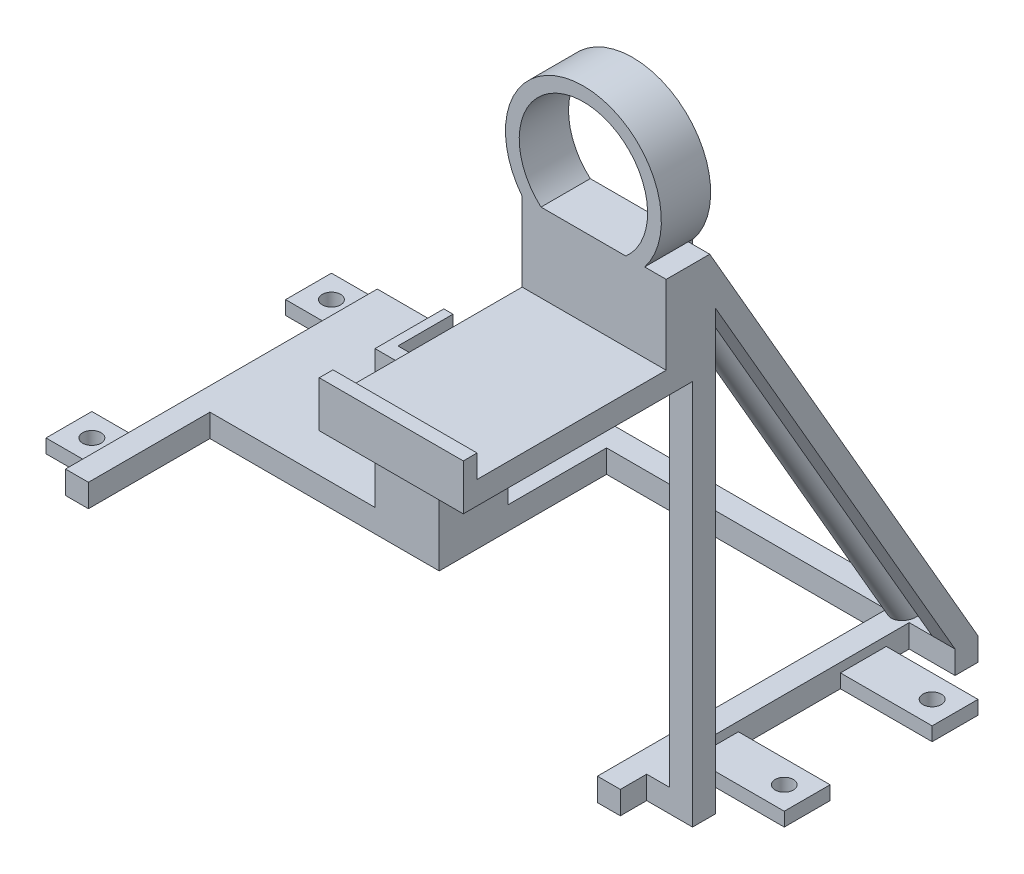
SolidWorks part; units mm, degrees
note: The reader was unsure of these and kept them because the rebuilt part matched: shared geometry of "Sketch23<2>".
ref_plane "Front Plane" through (0, 0, 0) normal (0, 0, 1) x (1, 0, 0)
ref_plane "Top Plane" through (0, 0, 0) normal (0, 1, 0) x (1, 0, 0)
ref_plane "Right Plane" through (0, 0, 0) normal (1, 0, 0) x (0, 0, -1)
sketch "Sketch1" plane through (0, 0, 0) normal (0, 1, 0) x (1, 0, 0)
  line L1 (0, 0) -> (121, 0)
  line L2 (0, 0) -> (0, -68)
  line L3 (0, -68) -> (121, -68)
  line L4 (121, 0) -> (121, -68)
  line L5 (5, -68) -> (116, -68)
  line L6 (5, -68) -> (5, -5)
  line L7 (5, -5) -> (116, -5)
  line L8 (116, -68) -> (116, -5)
  dimension "D1" = 121
  dimension "D2" = 68
  dimension "D3" = 5
  dimension "D4" = 5
  dimension "D5" = 5
extrude "Boss-Extrude1" add sketch "Sketch1" along normal blind 5 contours L8 L3 L4 L1 L2 L6 L7
ref_plane "Plane1" through (0, 3.75, 2.1651) normal (0, 0.866, 0.5) x (1, 0, 0)
sketch "Sketch2" plane through (0, 3.75, 2.1651) normal (0, 0.866, 0.5) x (1, 0, 0)
  line L2 (121, 2.5) -> (121, -56.3897) construction
  line L3 (0, 2.5) -> (121, 2.5) construction
  circle A0 centre (118.2001, -0.2999) radius 2.5
  dimension "D1" = 5
  dimension "D2" = 2.7999
  dimension "D3" = 2.7999
extrude "Boss-Extrude2" add sketch "Sketch2" along normal blind 100
ref_plane "Plane2" through (0, 0, 68) normal (0, 0, 1) x (1, 0, 0)
sketch "Sketch3" plane through (121, 0, 0) normal (1, 0, 0) x (0, 0, -1)
  line L0 (0, 5) -> (-68, 5) construction
  line L1 (0, 0) -> (-5, 0)
  line L2 (0, 0) -> (0, 5)
  line L3 (0, 5) -> (-5, 5)
  line L4 (-5, 0) -> (-5, 5)
  dimension "D1" = 5
extrude "Boss-Extrude3" add sketch "Sketch3" along normal blind 10
sketch "Sketch5" plane through (0, 3.75, 2.1651) normal (0, 0.866, 0.5) x (1, 0, 0)
  line L0 (131, -1.8301) -> (121, -1.8301) construction
  line L1 (131, 2.5) -> (126, 2.5)
  line L2 (131, 2.5) -> (131, -1.8301)
  line L3 (131, -1.8301) -> (126, -1.8301)
  line L4 (126, 2.5) -> (126, -1.8301)
  dimension "D1" = 5
extrude "Boss-Extrude4" add sketch "Sketch5" along normal offset from surface (117 mm away) 17 up to face at (118.2001, 88.9526, 54.5898) offset beyond the face yes
sketch "Sketch6" plane through (0, 1.25, -2.1651) normal (0, 0.5, -0.866) x (-1, 0, 0)
  line L0 (-126, 121.3301) -> (-126, 4.3301) construction
  line L1 (-131, 121.3301) -> (-126, 121.3301)
  line L2 (-131, 121.3301) -> (-131, 116.3301)
  line L3 (-131, 116.3301) -> (-126, 116.3301)
  line L4 (-126, 121.3301) -> (-126, 116.3301)
  dimension "D1" = 5
extrude "Boss-Extrude5" add sketch "Sketch6" along normal blind 20
sketch "Sketch7" plane through (126, 0, 0) normal (-1, 0, 0) x (0, 0, 1)
  line L0 (45.5096, 113.825) -> (41.1795, 116.325)
  line L1 (41.1795, 116.325) -> (62.25, 104.1599) construction
  line L2 (41.1795, 116.325) -> (38.6795, 111.9948)
  line L3 (38.6795, 111.9948) -> (43.0096, 109.4948)
  line L4 (38.6795, 111.9948) -> (56, 101.9948) construction
  line L5 (43.0096, 109.4948) -> (45.5096, 113.825)
  dimension "D1" = 90
  dimension "D2" = 5
extrude "Boss-Extrude6" add sketch "Sketch7" along normal blind 15
sketch "Sketch9" plane through (121, 0, 0) normal (1, 0, 0) x (0, 0, -1)
  line L0 (-62.25, 104.1599) -> (-62.25, 5) construction
  line L1 (-5, 5) -> (-68, 5) construction
  line L2 (-5, 0) -> (-68, 0) construction
  line L3 (-62.25, 5) -> (-57.25, 5)
  line L4 (-62.25, 5) -> (-62.25, 0)
  line L5 (-62.25, 0) -> (-57.25, 0)
  line L6 (-57.25, 5) -> (-57.25, 0)
  dimension "D1" = 5
extrude "Boss-Extrude7" add sketch "Sketch9" along normal up to surface (10 mm away) up to face at (131, 55.5593, 26.0136)
sketch "Sketch10" plane through (0, 5, 0) normal (0, 1, 0) x (1, 0, 0)
  line L0 (131, -57.25) -> (121, -57.25) construction
  line L1 (126, -57.25) -> (131, -57.25)
  line L2 (126, -57.25) -> (126, -62.25)
  line L3 (126, -62.25) -> (131, -62.25)
  line L4 (131, -57.25) -> (131, -62.25)
extrude "Boss-Extrude8" add sketch "Sketch10" along normal up to vertex
sketch "Sketch11" plane through (0, 0, 0) normal (-1, 0, 0) x (0, 0, 1)
  line L1 (62.25, 0) -> (52.25, 0)
  line L2 (62.25, 0) -> (62.25, 3)
  line L3 (62.25, 3) -> (52.25, 3)
  line L4 (52.25, 0) -> (52.25, 3)
  line L5 (0, 0) -> (10, 0)
  line L6 (0, 0) -> (0, 3)
  line L7 (0, 3) -> (10, 3)
  line L8 (10, 0) -> (10, 3)
  dimension "D1" = 10
  dimension "D2" = 3
  dimension "D3" = 10
  dimension "D4" = 3
extrude "Boss-Extrude9" add sketch "Sketch11" along normal blind 10
sketch "Sketch13" plane through (0, 3, 0) normal (0, 1, 0) x (1, 0, 0)
  line L0 (-5, -3) -> (-5, 0) construction
  line L1 (-10, 0) -> (0, 0) construction
  line L2 (-7, -5) -> (-10, -5) construction
  line L3 (-10, -10) -> (-10, 0) construction
  line L4 (-7, -57.25) -> (-10, -57.25) construction
  line L5 (-10, -62.25) -> (-10, -52.25) construction
  circle A0 centre (-5, -5) radius 2
  circle A1 centre (-5, -57.25) radius 2
  dimension "D1" = 4
extrude "Cut-Extrude1" cut sketch "Sketch13" against normal through all both and the other way through all
sketch "Sketch14" plane through (121, 0, 0) normal (1, 0, 0) x (0, 0, -1)
  line L0 (-5, 0) -> (-57.25, 0) construction
  line L1 (-20, 0) -> (-10, 0)
  line L2 (-20, 0) -> (-20, 3)
  line L3 (-20, 3) -> (-10, 3)
  line L4 (-10, 0) -> (-10, 3)
  line L5 (-57.25, 0) -> (-57.25, 5) construction
  line L6 (-42.25, 0) -> (-52.25, 0)
  line L7 (-42.25, 0) -> (-42.25, 3)
  line L8 (-42.25, 3) -> (-52.25, 3)
  line L9 (-52.25, 0) -> (-52.25, 3)
  line L10 (-5, 5) -> (-5, 0) construction
  dimension "D1" = 10
  dimension "D2" = 3
  dimension "D3" = 10
  dimension "D4" = 3
  dimension "D5" = 5
  dimension "D6" = 5
extrude "Boss-Extrude10" add sketch "Sketch14" along normal blind 20
sketch "Sketch15" plane through (0, 3, 0) normal (0, 1, 0) x (1, 0, 0)
  line L0 (138, -15) -> (141, -15) construction
  line L1 (141, -10) -> (141, -20) construction
  line L2 (136, -13) -> (136, -10) construction
  line L3 (141, -10) -> (121, -10) construction
  line L4 (136, -45.25) -> (136, -42.25) construction
  line L5 (141, -42.25) -> (121, -42.25) construction
  line L6 (138, -47.25) -> (141, -47.25) construction
  line L7 (141, -42.25) -> (141, -52.25) construction
  circle A0 centre (136, -15) radius 2
  circle A1 centre (136, -47.25) radius 2
  point P22 (141, -47.25)
  dimension "D1" = 4
extrude "Cut-Extrude2" cut sketch "Sketch15" against normal through all both and the other way through all
sketch "Sketch16" plane through (126, 0, 0) normal (-1, 0, 0) x (0, 0, 1)
  line L0 (49.8397, 111.325) -> (67, 101.4175)
  line L1 (49.8397, 111.325) -> (47.3397, 106.9948)
  line L2 (67, 101.4175) -> (64.5, 97.0874)
  line L3 (47.3397, 106.9948) -> (64.5, 97.0874)
  line L4 (45.5096, 113.825) -> (62.25, 104.1599) construction
  line L5 (43.0096, 109.4948) -> (56, 101.9948) construction
  line L6 (68, -54.223) -> (68, 54.223) construction
  line L7 (43.0096, 109.4948) -> (45.5096, 113.825) construction
  point P13 (44.2596, 111.6599)
  dimension "D1" = 1
  dimension "D2" = 90
  dimension "D3" = 5
extrude "Boss-Extrude11" add sketch "Sketch16" along normal blind 7.8
sketch "Sketch17" plane through (0, 105.075, 60.6651) normal (0, 0.866, 0.5) x (1, 0, 0)
  line L1 (131, 22.5) -> (108.821, 22.5)
  line L2 (131, 22.5) -> (131, 2.5)
  line L3 (131, 2.5) -> (108.821, 2.5)
  line L4 (108.821, 22.5) -> (108.821, 2.5)
  line L5 (0, 2.5) -> (126, 2.5) construction
extrude "Cut-Extrude3" cut sketch "Sketch17" against normal through all both and the other way through all
sketch "Sketch18" plane through (0, 0, 62.25) normal (0, 0, 1) x (1, 0, 0)
  line L0 (126, 104.1599) -> (118.2, 104.1599)
  line L1 (118.2, 104.1599) -> (102.2, 104.1599) construction
  line L2 (102.2, 104.1599) -> (100.7, 104.1599)
  arc A0 (102.2, 104.1599) -> (118.2, 104.1599) centre (110.2, 104.1599) cw
  arc A1 (100.7, 104.1599) -> (119.7, 104.1599) centre (110.2, 104.1599) cw
  dimension "D1" = 7.8
  dimension "D2" = 16
  dimension "D3" = 1.5
extrude "Boss-Extrude12" add sketch "Sketch18" along normal up to surface (5.75 mm away) and the other way blind 5 separate body contours A1 L2 A0 L0 up to plane "Plane2"
sketch "Sketch19" plane through (0, 104.1599, 0) normal (0, -1, 0) x (1, 0, 0)
  line L4 (119.7, 57.25) -> (119.7, 68)
  line L5 (119.7, 68) -> (118.2, 68)
  line L6 (118.2, 68) -> (118.2, 57.25)
  line L7 (118.2, 57.25) -> (119.7, 57.25)
  line L8 (119.7, 57.25) -> (119.7, 68)
  line L9 (119.7, 68) -> (118.2, 68)
  line L10 (118.2, 68) -> (118.2, 57.25)
  line L11 (118.2, 57.25) -> (119.7, 57.25)
  dimension "D1" = 0
extrude "Boss-Extrude13" add sketch "Sketch19" along normal up to vertex (2.7424 mm away) up to point (118.2, 101.4175, 67)
sketch "Sketch20" plane through (0, -3.6575, 6.3349) normal (0, -0.5, 0.866) x (1, 0, 0)
  line L5 (126, 116.3301) -> (126, 121.3301)
  line L6 (126, 121.3301) -> (119.7, 121.3301)
  line L7 (119.7, 121.3301) -> (118.2, 121.3301)
  line L8 (118.2, 121.3301) -> (118.2, 116.3301)
  line L9 (118.2, 116.3301) -> (126, 116.3301)
  line L10 (126, 116.3301) -> (126, 121.3301)
  line L11 (126, 121.3301) -> (119.7, 121.3301)
  line L12 (119.7, 121.3301) -> (118.2, 121.3301)
  line L13 (118.2, 121.3301) -> (118.2, 116.3301)
  line L14 (118.2, 116.3301) -> (126, 116.3301)
  dimension "D1" = 0
sketch "Sketch21" plane through (0, 101.4175, 0) normal (0, -1, 0) x (1, 0, 0)
  line L4 (118.2, 67) -> (119.7, 67)
  line L5 (119.7, 67) -> (119.7, 68)
  line L6 (119.7, 68) -> (118.2, 68)
  line L7 (118.2, 68) -> (118.2, 67)
  line L9 (119.7, 67) -> (119.7, 68)
  line L10 (119.7, 68) -> (118.2, 68)
  line L11 (118.2, 68) -> (118.2, 67)
  line L12 (118.2, 67) -> (119.7, 67)
  dimension "D1" = 0
extrude "Boss-Extrude15" add sketch "Sketch21" along normal blind 1
extrude "Boss-Extrude17" add sketch "Sketch20" against normal up to surface (1.1547 mm away)
ref_plane "Plane3" through (0, 104.1599, 0) normal (0, -1, 0) x (-1, 0, 0)
sketch "Sketch23" plane through (0, 104.1599, 0) normal (0, -1, 0) x (-1, 0, 0)
  line L1 (-126, -56) -> (-118.2, -56)
  line L2 (-126, -56) -> (-126, -68)
  line L3 (-126, -68) -> (-118.2, -68)
  line L4 (-118.2, -56) -> (-118.2, -68)
  dimension "D1" = 7.8
  dimension "D2" = 12
extrude "Cut-Extrude4" cut sketch "Sketch23" along normal blind 10 from offset 2
extrude "Boss-Extrude19" add sketch "Sketch23<2>" along normal blind 5 and the other way up to vertex (2.1651 mm away) other way up to point (119.45, 106.325, 58.5)
sketch "Sketch23<2>" plane through (0, 104.1599, 0) normal (0, -1, 0) x (-1, 0, 0) same geometry as "Sketch23"
sketch "Sketch24" plane through (0, 0, 56) normal (0, 0, -1) x (-1, 0, 0)
  line L5 (-126, 106.325) -> (-126, 101.9948)
  line L6 (-126, 101.9948) -> (-126, 99.1599)
  line L7 (-126, 99.1599) -> (-118.2, 99.1599)
  line L8 (-118.2, 99.1599) -> (-118.2, 106.325)
  line L9 (-118.2, 106.325) -> (-126, 106.325)
  line L10 (-126, 106.325) -> (-126, 101.9948)
  line L11 (-126, 101.9948) -> (-126, 99.1599)
  line L12 (-126, 99.1599) -> (-118.2, 99.1599)
  line L13 (-118.2, 99.1599) -> (-118.2, 106.325)
  line L14 (-118.2, 106.325) -> (-126, 106.325)
  dimension "D1" = 0
extrude "Cut-Extrude5" cut sketch "Sketch24" against normal up to surface (1.25 mm away) up to face at (111.5571, 108.2969, 57.25)
sketch "Sketch25" plane through (0, 105.075, 60.6651) normal (0, 0.866, 0.5) x (1, 0, 0)
  line L4 (126, 2.5) -> (126, -1.8301)
  line L5 (126, -1.8301) -> (131, -1.8301)
  line L6 (131, -1.8301) -> (131, 2.5)
  line L7 (131, 2.5) -> (126, 2.5)
  line L8 (126, 2.5) -> (126, -1.8301)
  line L9 (126, -1.8301) -> (131, -1.8301)
  line L10 (131, -1.8301) -> (131, 2.5)
  line L11 (131, 2.5) -> (126, 2.5)
  dimension "D1" = 0
extrude "Boss-Extrude20" add sketch "Sketch25" along normal up to surface (2.5 mm away) up to face at (123.38, 106.325, 61.8)
sketch "Sketch26" plane through (0, 0, 62.25) normal (0, 0, 1) x (1, 0, 0)
  line L1 (131, 104.1599) -> (126, 104.1599)
  line L2 (131, 104.1599) -> (131, 106.325)
  line L3 (131, 106.325) -> (126, 106.325)
  line L4 (126, 104.1599) -> (126, 106.325)
extrude "Cut-Extrude6" cut sketch "Sketch26" along normal blind 5
sketch "Sketch27" plane through (126, 0, 0) normal (1, 0, 0) x (0, 0, -1)
  line L4 (-62.25, 99.1599) -> (-62.25, 106.325)
  line L5 (-62.25, 106.325) -> (-68, 106.325)
  line L6 (-68, 106.325) -> (-68, 99.1599)
  line L7 (-68, 99.1599) -> (-62.25, 99.1599)
  line L8 (-62.25, 99.1599) -> (-62.25, 106.325)
  line L9 (-62.25, 106.325) -> (-68, 106.325)
  line L10 (-68, 106.325) -> (-68, 99.1599)
  line L11 (-68, 99.1599) -> (-62.25, 99.1599)
  dimension "D1" = 0
extrude "Boss-Extrude21" add sketch "Sketch27" along normal up to surface (5 mm away) up to face at (131, 35.35, 34.1667)
sketch "Sketch29" plane through (0, 0, 0) normal (-1, 0, 0) x (0, 0, 1)
  line L0 (26, 0) -> (26, 35) construction
  line L1 (10, 0) -> (52.25, 0) construction
  line L2 (0, 5) -> (0, 3) construction
  line L3 (0, 5) -> (68, 5) construction
  line L4 (38.5, 5) -> (38.5, 35)
  line L6 (38.5, 35) -> (41.5, 35)
  line L7 (38.5, 35) -> (38.5, 5)
  line L8 (38.5, 5) -> (41.5, 5)
  line L9 (41.5, 35) -> (41.5, 5)
  line M7 (68, 5) -> (0, 5)
  dimension "D1" = 30
  dimension "D2" = 26
  dimension "D3" = 35
  dimension "D4" = 12.5
  dimension "D5" = 12.5
  dimension "D6" = 3
extrude "Boss-Extrude22" add sketch "Sketch29" against normal blind 55 contours L9 L6 L4 M7
sketch "Sketch30" plane through (0, 5, 0) normal (0, -1, 0) x (1, 0, 0)
  line L0 (55, 41.5) -> (5, 41.5) construction
  line L1 (55, 38.5) -> (50, 38.5)
  line L2 (55, 38.5) -> (55, 41.5)
  line L3 (55, 41.5) -> (50, 41.5)
  line L4 (50, 38.5) -> (50, 41.5)
  dimension "D1" = 5
extrude "Boss-Extrude23" add sketch "Sketch30" along normal up to surface (5 mm away) up to face at (136, 0, 17)
sketch "Sketch31" plane through (0, 0, 38.5) normal (0, 0, -1) x (-1, 0, 0)
  line L0 (10, 0) -> (-131, 0) construction
  line L1 (-50, 5) -> (-55, 5)
  line L2 (-50, 5) -> (-50, 0)
  line L3 (-50, 0) -> (-55, 0)
  line L4 (-55, 5) -> (-55, 0)
  line L5 (-55, 0) -> (-55, 35) construction
extrude "Boss-Extrude24" add sketch "Sketch31" along normal up to surface (33.5 mm away) up to face at (60.5, 2.5, 5)
sketch "Sketch32" plane through (0, 0, 38.5) normal (0, 0, -1) x (-1, 0, 0)
  line L0 (-53, 9) -> (-41, 9)
  line L1 (-55, 35) -> (-55, 7)
  line L2 (-53, 35) -> (-57, 35)
  line L3 (-57, 35) -> (-57, 9)
  line L4 (-41, 7) -> (-69, 7)
  line L5 (-67, 35) -> (-67, 16)
  line L6 (-67, 35) -> (-69, 35)
  line L7 (-69, 35) -> (-69, 16)
  line L8 (-67, 16) -> (-69, 16)
  line L10 (-41, 7) -> (-41, 9)
  line L13 (-69, 7) -> (-69, 9)
  line L14 (-57, 9) -> (-69, 9)
  line L16 (-43, 16) -> (-41, 16)
  line L17 (-41, 35) -> (-41, 16)
  line L18 (-43, 35) -> (-41, 35)
  line L19 (-43, 35) -> (-43, 16)
  line L20 (-53, 35) -> (-53, 9)
  line M7 (0, 35) -> (-55, 35)
  line M8 (-55, 35) -> (-55, 5)
  dimension "D2" = 10
  dimension "D3" = 2
  dimension "D4" = 19
extrude "Boss-Extrude25" add sketch "Sketch32" along normal blind 12 contours L20 L4 L10 L0 M7 M8 | L19 L16 L17 M7
sketch "Sketch34" plane through (0, 35, 0) normal (0, 1, 0) x (1, 0, 0)
  line L1 (41, -38.5) -> (0, -38.5)
  line L2 (41, -38.5) -> (41, -41.5)
  line L3 (41, -41.5) -> (0, -41.5)
  line L4 (0, -38.5) -> (0, -41.5)
extrude "Cut-Extrude7" cut sketch "Sketch34" against normal up to surface (30 mm away) up to face at (118.2001, 5, 0.3463)
sketch "Sketch35" plane through (0, 7, 0) normal (0, -1, 0) x (1, 0, 0)
  line L4 (55, 38.5) -> (41, 38.5)
  line L5 (41, 38.5) -> (41, 26.5)
  line L6 (41, 26.5) -> (55, 26.5)
  line L7 (55, 26.5) -> (55, 38.5)
  line L8 (55, 38.5) -> (41, 38.5)
  line L9 (41, 38.5) -> (41, 26.5)
  line L10 (41, 26.5) -> (55, 26.5)
  line L11 (55, 26.5) -> (55, 38.5)
  dimension "D1" = 0
extrude "Boss-Extrude26" add sketch "Sketch35" along normal up to surface (7 mm away) up to face at (136, 0, 17)
sketch "Sketch36" plane through (0, 0, 38.5) normal (0, 0, 1) x (1, 0, 0)
  line L4 (50, 0) -> (50, 5)
  line L5 (50, 5) -> (41, 5)
  line L6 (41, 5) -> (41, 0)
  line L7 (41, 0) -> (50, 0)
  line L8 (50, 0) -> (50, 5)
  line L9 (50, 5) -> (41, 5)
  line L10 (41, 5) -> (41, 0)
  line L11 (41, 0) -> (50, 0)
  dimension "D1" = 0
extrude "Boss-Extrude27" add sketch "Sketch36" along normal up to surface and the other way up to surface up to face at (48.6667, 13.3333, 41.5) other way up to face at (27.5, 2.5, 5)
sketch "Sketch37" plane through (41, 0, 0) normal (-1, 0, 0) x (0, 0, 1)
  line L1 (41.5, 0) -> (0, 0)
  line L2 (41.5, 0) -> (41.5, 5)
  line L3 (41.5, 5) -> (0, 5)
  line L4 (0, 0) -> (0, 5)
extrude "Boss-Extrude28" add sketch "Sketch37" along normal up to surface (41 mm away) contours L2 L1 L4 L3 up to face at (0, 2.2, 38.5)
sketch "Sketch38" plane through (118.2, 0, 0) normal (-1, 0, 0) x (0, 0, 1)
  line L1 (44.0573, 123.2063) -> (78.3089, 123.2063)
  line L2 (44.0573, 123.2063) -> (44.0573, 96.1184)
  line L3 (44.0573, 96.1184) -> (78.3089, 96.1184)
  line L4 (78.3089, 123.2063) -> (78.3089, 96.1184)
extrude "Cut-Extrude8" cut sketch "Sketch38" along normal through all
sketch "Sketch39" plane through (0, 106.325, 0) normal (0, 1, 0) x (1, 0, 0)
  line L1 (86.6562, -42.2101) -> (154.3408, -42.2101)
  line L2 (86.6562, -42.2101) -> (86.6562, -72.2403)
  line L3 (86.6562, -72.2403) -> (154.3408, -72.2403)
  line L4 (154.3408, -42.2101) -> (154.3408, -72.2403)
extrude "Cut-Extrude9" cut sketch "Sketch39" along normal through all
sketch "Sketch42" plane through (0, 0, 68) normal (0, 0, 1) x (1, 0, 0)
  line L4 (131, 106.325) -> (118.2, 106.325)
  line L5 (118.2, 106.325) -> (118.2, 99.1599)
  line L6 (118.2, 99.1599) -> (131, 99.1599)
  line L7 (131, 99.1599) -> (131, 106.325)
  line L8 (131, 106.325) -> (118.2, 106.325)
  line L9 (118.2, 106.325) -> (118.2, 99.1599)
  line L10 (118.2, 99.1599) -> (131, 99.1599)
  line L11 (131, 99.1599) -> (131, 106.325)
  dimension "D1" = 0
sketch "Sketch43" plane through (0, 0, 57.25) normal (0, 0, -1) x (-1, 0, 0)
  line L0 (-120.7001, 90.2026) -> (-120.7001, 106.325) construction
  line L1 (-120.7001, 106.325) -> (-122.2001, 106.325) construction
  line L2 (-122.2001, 106.325) -> (-122.2001, 90.2026) construction
  line L3 (-122.2001, 90.2026) -> (-120.7001, 90.2026) construction
  line L4 (-118.2, 106.325) -> (-126, 106.325) construction
  line L5 (-120.7001, 106.325) -> (-104.7001, 106.325) construction
  line L6 (-104.7001, 106.325) -> (-103.7001, 106.325) construction
  line L7 (-104.7001, 106.325) -> (-104.7001, 90.2026) construction
  line L8 (-104.7001, 90.2026) -> (-103.7001, 90.2026) construction
  line L9 (-103.7001, 90.2026) -> (-103.7001, 106.325) construction
  line L10 (-122.2001, 106.325) -> (-126, 106.325)
  line L11 (-103.7001, 106.325) -> (-99.5874, 106.325)
  line L16 (-126, 106.325) -> (-126.3129, 106.325)
  arc A0 (-122.2001, 106.325) -> (-103.7001, 106.325) centre (-112.9501, 116.8339) cw
  arc A1 (-126.3129, 106.325) -> (-99.5874, 106.325) centre (-112.9501, 116.8339) cw
  arc A2 (-124.1823, 104.0731) -> (-101.718, 104.0731) centre (-112.9501, 116.8339) cw construction
  point P18 (0, 0)
  dimension "D4" = 14
  dimension "D1" = 1.5
  dimension "D2" = 16
  dimension "D3" = 1
  dimension "D5" = 3
sketch "Sketch44" plane through (118.2, 0, 0) normal (-1, 0, 0) x (0, 0, 1)
  line L1 (57.25, 106.325) -> (62.25, 106.325)
  line L2 (57.25, 106.325) -> (57.25, 99.1599)
  line L3 (57.25, 99.1599) -> (62.25, 99.1599)
  line L4 (62.25, 106.325) -> (62.25, 99.1599)
extrude "Boss-Extrude30" add sketch "Sketch44" along normal up to vertex (18.6126 mm away) up to point (99.5874, 106.325, 57.25)
extrude "Boss-Extrude31" add sketch "Sketch43" against normal up to surface (10.75 mm away) up to plane "Plane2"
sketch "Sketch45" plane through (0, 0, 62.25) normal (0, 0, 1) x (1, 0, 0)
  line L5 (118.2, 99.1599) -> (118.2, 106.325)
  line L6 (118.2, 106.325) -> (103.7001, 106.325)
  line L7 (103.7001, 106.325) -> (99.5874, 106.325)
  line L8 (99.5874, 106.325) -> (99.5874, 99.1599)
  line L9 (99.5874, 99.1599) -> (118.2, 99.1599)
  line L10 (118.2, 99.1599) -> (118.2, 106.325)
  line L11 (118.2, 106.325) -> (103.7001, 106.325)
  line L12 (103.7001, 106.325) -> (99.5874, 106.325)
  line L13 (99.5874, 106.325) -> (99.5874, 99.1599)
  line L14 (99.5874, 99.1599) -> (118.2, 99.1599)
  dimension "D1" = 0
extrude "Boss-Extrude32" add sketch "Sketch45" along normal up to surface (5.75 mm away) up to face at (118.7751, 111.0359, 68)
sketch "Sketch46" plane through (0, 0, 62.25) normal (0, 0, 1) x (1, 0, 0)
  line L0 (126, 99.1599) -> (126, 5) construction
  line L1 (126, 89.1599) -> (131, 89.1599)
  line L2 (126, 89.1599) -> (126, 84.1599)
  line L3 (126, 84.1599) -> (131, 84.1599)
  line L4 (131, 89.1599) -> (131, 84.1599)
  line L5 (131, 99.1599) -> (131, 0) construction
  line L6 (118.2, 99.1599) -> (131, 99.1599) construction
  dimension "D1" = 5
  dimension "D2" = 10
extrude "EDIT THIS LENGTH" add sketch "Sketch46" along normal blind 50
sketch "Sketch47" plane through (0, 89.1599, 0) normal (0, 1, 0) x (1, 0, 0)
  line L0 (126, -112.25) -> (126, -62.25) construction
  line L1 (126, -109.25) -> (131, -109.25)
  line L2 (126, -109.25) -> (126, -112.25)
  line L3 (126, -112.25) -> (131, -112.25)
  line L4 (131, -109.25) -> (131, -112.25)
  dimension "D1" = 3
extrude "Boss-Extrude34" add sketch "Sketch47" along normal blind 5
sketch "Sketch48" plane through (0, 99.1599, 0) normal (0, -1, 0) x (1, 0, 0)
  line L0 (131, 62.25) -> (126, 62.25) construction
  line L1 (126, 62.75) -> (99.5874, 62.75)
  line L2 (126, 62.75) -> (126, 68)
  line L3 (126, 68) -> (99.5874, 68)
  line L4 (99.5874, 62.75) -> (99.5874, 68)
  line L7 (126, 57.25) -> (126, 62.25) construction
  dimension "D1" = 0.5
extrude "Boss-Extrude35" add sketch "Sketch48" along normal up to surface (15 mm away) up to face at (128.5, 84.1599, 87.25)
sketch "Sketch50" plane through (0, 99.1599, 0) normal (0, -1, 0) x (1, 0, 0)
  line L1 (126, 62.25) -> (131, 62.25)
  line L2 (126, 62.25) -> (126, 68)
  line L3 (126, 68) -> (131, 68)
  line L4 (131, 62.25) -> (131, 68)
extrude "Boss-Extrude36" add sketch "Sketch50" along normal up to surface (10 mm away) up to face at (127.6667, 89.1599, 78.9583)
sketch "Sketch51" plane through (126, 0, 0) normal (-1, 0, 0) x (0, 0, 1)
  line L6 (68, 89.1599) -> (68, 84.1599)
  line L7 (68, 84.1599) -> (112.25, 84.1599)
  line L8 (112.25, 84.1599) -> (112.25, 94.1599)
  line L9 (112.25, 94.1599) -> (109.25, 94.1599)
  line L10 (109.25, 94.1599) -> (109.25, 89.1599)
  line L11 (109.25, 89.1599) -> (68, 89.1599)
  line L12 (68, 89.1599) -> (68, 84.1599)
  line L13 (68, 84.1599) -> (112.25, 84.1599)
  line L14 (112.25, 84.1599) -> (112.25, 94.1599)
  line L15 (112.25, 94.1599) -> (109.25, 94.1599)
  line L16 (109.25, 94.1599) -> (109.25, 89.1599)
  line L17 (109.25, 89.1599) -> (68, 89.1599)
  dimension "D1" = 0
extrude "Boss-Extrude37" add sketch "Sketch51" along normal up to surface (26.4126 mm away) up to face at (99.5874, 96.5483, 62.6667)
chamfer "Chamfer1" distance 16 angle 5 1 edges at (99.5874, 99.1599, 60) first distance on face at (112.7937, 99.1599, 60)
